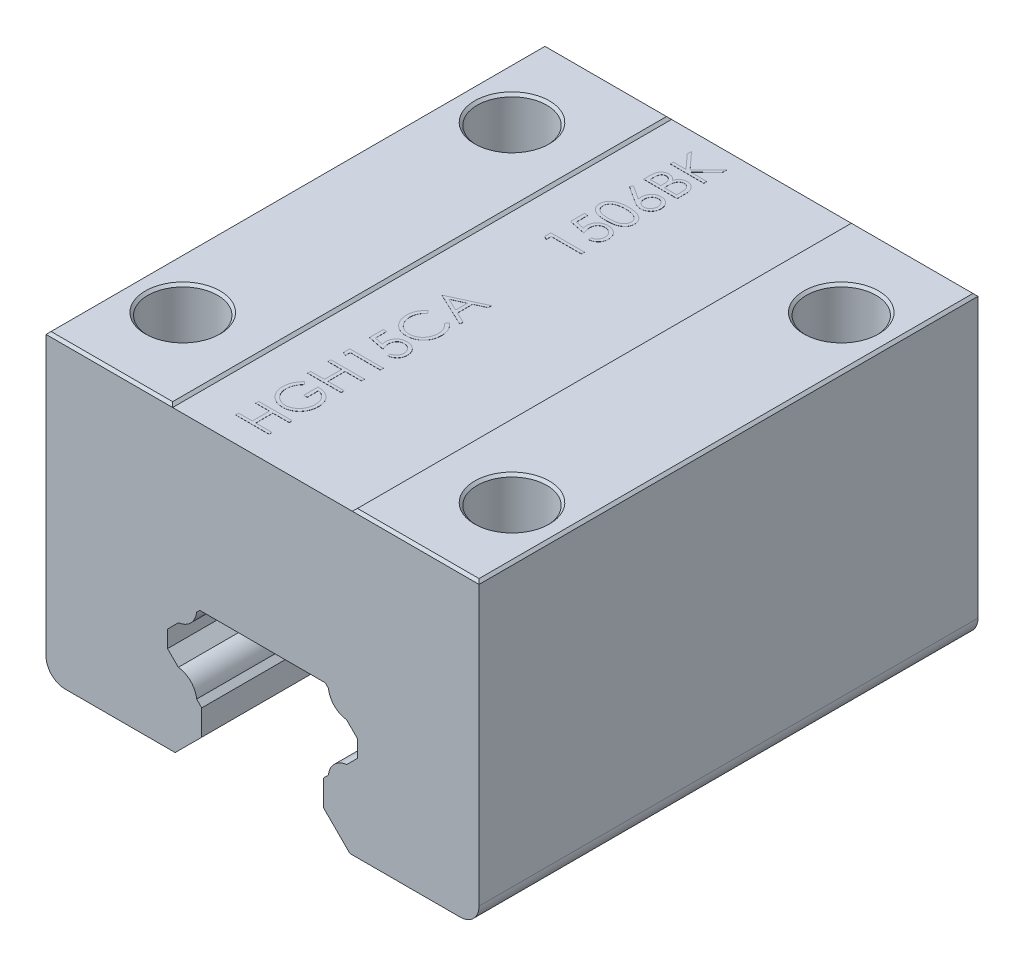
SolidWorks part; units mm, degrees
material "AISI Тип A2 Инструментальная сталь"
ref_plane "Спереди" through (0, 0, 0) normal (0, 0, 1) x (1, 0, 0)
ref_plane "Сверху" through (0, 0, 0) normal (0, 1, 0) x (1, 0, 0)
ref_plane "Справа" through (0, 0, 0) normal (1, 0, 0) x (0, 0, -1)
sketch "Model" plane through (0, 0, 0) normal (0, 0, 1) x (1, 0, 0)
  line L0 (-17.0982, 0) -> (-17.0982, -50000) construction
  line L1 (17.0982, 1.078) -> (17.0982, -49998.922) construction
  line L2 (0, 10.7) -> (0, -49989.3) construction
  line L3 (-6.1277, 0) -> (-50006.1277, 0) construction
  line L4 (0, 23.7) -> (50000, 23.7) construction
  line L5 (-17.0982, 1.5) -> (-17.0982, 23.7)
  line L6 (17.0982, 1.5) -> (17.0982, 23.7)
  line L7 (6.8994, 0) -> (15.5982, 0)
  line L8 (0.9726, 23.5) -> (50000.9726, 23.5) construction
  line L9 (-7.0982, 28.8935) -> (-7.0982, -49971.1065) construction
  line L10 (7.0982, 29.5448) -> (7.0982, -49970.4552) construction
  line L11 (-7.0982, 23.7) -> (-7.0982, 23.5)
  line L12 (-7.0982, 23.5) -> (7.0982, 23.5)
  line L13 (7.0982, 23.5) -> (7.0982, 23.7)
  line L24 (17.0982, 23.7) -> (7.0982, 23.7)
  line L32 (-7.0982, 23.7) -> (-17.0982, 23.7)
  line L146 (4.7998, 2.0996) -> (6.8994, 0)
  line L155 (-6.8994, 0) -> (-15.5982, 0)
  line L156 (-6.8994, 0) -> (-4.7998, 2.0996)
  line L157 (-4.7998, 2.0996) -> (-4.7998, 4.1091)
  line L158 (-4.7998, 4.1091) -> (-5.2008, 4.5101)
  line L159 (-6.6481, 5.9574) -> (-7.5, 6.8093)
  line L160 (-7.5, 6.8093) -> (-7.5, 8.1495)
  line L161 (-7.5, 8.1495) -> (-6.6345, 9.015)
  line L162 (-5.2023, 10.4472) -> (-4.9495, 10.7)
  line L163 (-4.9495, 10.7) -> (4.9495, 10.7)
  line L164 (4.9495, 10.7) -> (5.2023, 10.4472)
  line L165 (6.6345, 9.015) -> (7.5, 8.1495)
  line L166 (7.5, 8.1495) -> (7.5, 6.8093)
  line L167 (7.5, 6.8093) -> (6.6481, 5.9574)
  line L168 (5.2008, 4.5101) -> (4.7998, 4.1091)
  line L169 (4.7998, 4.1091) -> (4.7998, 2.0996)
  arc A0 (15.5982, 0) -> (17.0982, 1.5) centre (15.5982, 1.5) ccw
  arc A12 (-17.0982, 1.5) -> (-15.5982, 0) centre (-15.5982, 1.5) ccw
  arc A13 (-5.2008, 4.5101) -> (-6.6481, 5.9574) centre (-6.8215, 4.3367) ccw
  arc A14 (-6.6345, 9.015) -> (-5.2023, 10.4472) centre (-6.8215, 10.6342) ccw
  arc A15 (5.2023, 10.4472) -> (6.6345, 9.015) centre (6.8215, 10.6342) ccw
  arc A16 (6.6481, 5.9574) -> (5.2008, 4.5101) centre (6.8215, 4.3367) ccw
  point P57 (0, 10.7)
  dimension "D1" = 34.1964
  dimension "D2" = 23.7
  dimension "D3" = 10
  dimension "D4" = 10
  dimension "D5" = 0.2
extrude "Бобышка-Вытянуть1" add sketch "Model" along normal blind 39.4
sketch "Эскиз3" plane through (0, 23.7, 0) normal (0, -1, 0) x (1, 0, 0)
  line L1 (-19, 32.7) -> (49981, 32.7) construction
  line L2 (-18.1533, 6.7) -> (49981.8467, 6.7) construction
  line L3 (-13, 33.585) -> (-13, -49966.415) construction
  line L7 (13, 27.6372) -> (13, -49972.3628) construction
  line L8 (-6.8994, 19.7) -> (-50006.8994, 19.7) construction
  line L9 (-6.8994, 39.4) -> (-6.8994, 0) construction
  line L10 (0, 39.4) -> (0, -49960.6) construction
  line L12 (-4.9495, 39.4) -> (4.9495, 39.4) construction
  circle A0 centre (-13, 32.7) radius 2.75
  circle A1 centre (-13, 6.7) radius 2.75
  circle A2 centre (13, 6.7) radius 2.75
  circle A3 centre (13, 32.7) radius 2.75
  point P19 (-6.8994, 19.7)
  point P28 (0, 39.4)
  dimension "D1" = 26
  dimension "D3" = 13
  dimension "D4" = 13
  dimension "D2" = 26
extrude "Вырез-Вытянуть2" cut sketch "Эскиз3" along normal blind 5
chamfer "Фаска1" distance 0.2 angle 45 12 edges at (-12.0982, 23.7, 0) (-7.0982, 23.7, 19.7) (-12.0982, 23.7, 39.4) (-17.0982, 23.7, 19.7) (12.0982, 23.7, 0) (7.0982, 23.7, 19.7) (12.0982, 23.7, 39.4) (17.0982, 23.7, 19.7) (-10.25, 23.7, 6.7) (15.75, 23.7, 6.7) (15.75, 23.7, 32.7) (-10.25, 23.7, 32.7)
sketch "Эскиз4" plane through (0, 23.5, 0) normal (0, 1, 0) x (1, 0, 0)
  line L0 (-1.4592, -38.7831) -> (-1.4592, -2.2979) construction
  text T0 " HGH15CA      1506BK-5E" font "Century Gothic" height in points 10
  point P3 (-1.4592, -38.7831)
extrude "Бобышка-Вытянуть2" add sketch "Эскиз4" along normal blind 0.01
